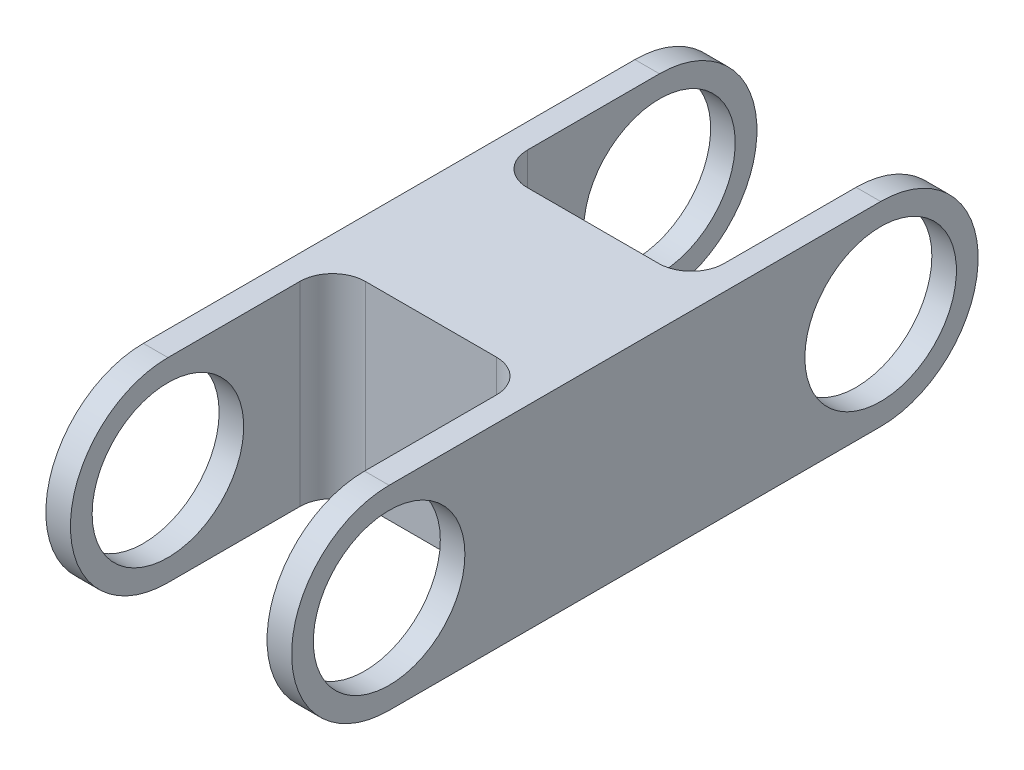
SolidWorks part; units mm, degrees
ref_plane "Front Plane" through (0, 0, 0) normal (0, 0, 1) x (1, 0, 0)
ref_plane "Top Plane" through (0, 0, 0) normal (0, 1, 0) x (1, 0, 0)
ref_plane "Right Plane" through (0, 0, 0) normal (1, 0, 0) x (0, 0, -1)
sketch "Sketch1" plane through (0, 0, 0) normal (1, 0, 0) x (0, 0, -1)
  line L0 (0, 11.9) -> (60, 11.9)
  line L1 (0, -11.9) -> (60, -11.9)
  line L2 (30, 11.9) -> (30, -11.9) construction
  circle A0 centre (0, 0) radius 9.25
  arc A1 (0, 11.9) -> (0, -11.9) centre (0, 0) ccw
  circle A2 centre (60, 0) radius 9.25
  arc A3 (60, 11.9) -> (60, -11.9) centre (60, 0) cw
  dimension "D1" = 18.5
  dimension "D2" = 23.8
  dimension "D3" = 60
extrude "Boss-Extrude1" add sketch "Sketch1" along normal blind 30
sketch "Sketch2" plane through (0, 11.9, 0) normal (0, 1, 0) x (1, 0, 0)
  line L0 (0, -11.9) -> (30, -11.9) construction
  line L1 (3, -11.9) -> (27, -11.9)
  line L2 (3, -11.9) -> (3, 20.1)
  line L3 (3, 20.1) -> (27, 20.1)
  line L4 (27, -11.9) -> (27, 20.1)
  line L5 (0, 30) -> (30, 30) construction
  line L6 (0, 60) -> (0, 0) construction
  line L7 (30, 60) -> (30, 0) construction
  line L8 (3, 39.9) -> (27, 39.9)
  line L9 (27, 71.9) -> (27, 39.9)
  line L10 (3, 71.9) -> (27, 71.9)
  line L11 (3, 71.9) -> (3, 39.9)
  dimension "D1" = 32
  dimension "D2" = 3
  dimension "D3" = 3
extrude "Cut-Extrude1" cut sketch "Sketch2" against normal through all
ref_plane "Plane1" through (0, 0, -30) normal (0, 0, 1) x (1, 0, 0)
fillet "Fillet1" radius 4 4 edges at (27, 0, -20.1) (3, 0, -20.1) (27, 0, -39.9) (3, 0, -39.9)
